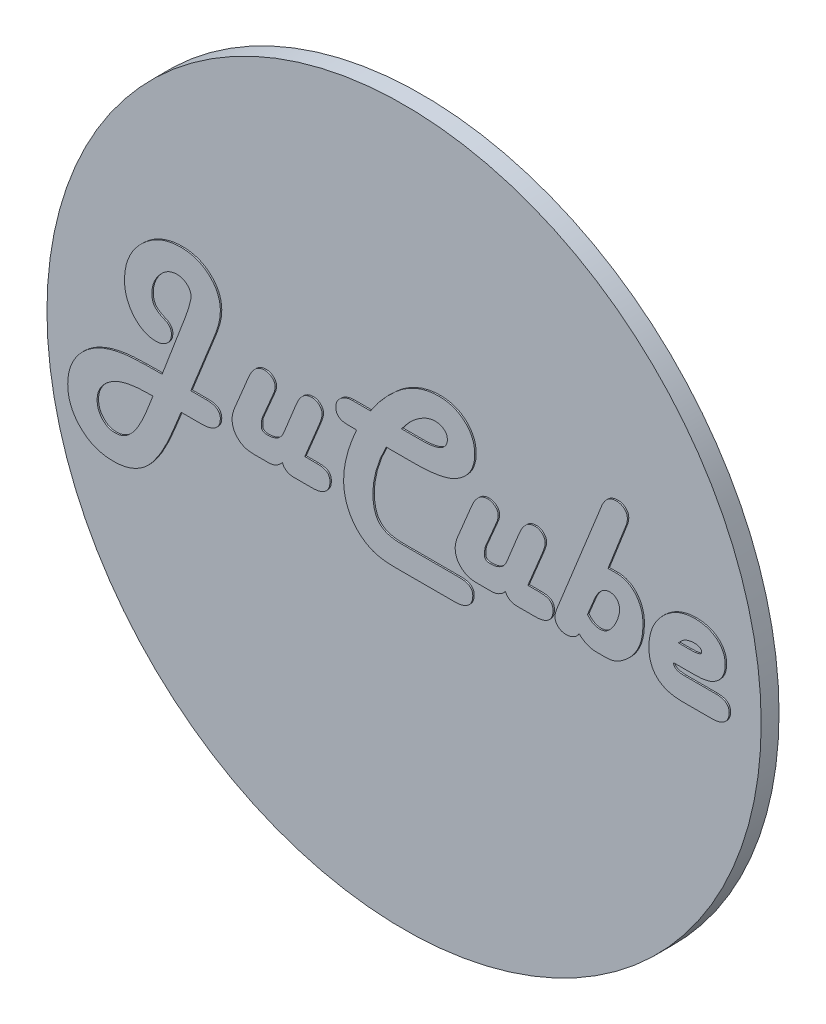
SolidWorks part; units mm, degrees
ref_plane "Front Plane" through (0, 0, 0) normal (0, 0, 1) x (1, 0, 0)
ref_plane "Top Plane" through (0, 0, 0) normal (0, 1, 0) x (1, 0, 0)
ref_plane "Right Plane" through (0, 0, 0) normal (1, 0, 0) x (0, 0, -1)
sketch "Sketch2" plane through (0, 0, 0) normal (0, 0, 1) x (1, 0, 0)
  circle A0 centre (0, 0) radius 63.5
  dimension "D1" = 127
extrude "Boss-Extrude1" add sketch "Sketch2" along normal blind 3.175
sketch "Sketch3" plane through (0, 0, 3.175) normal (0, 0, 1) x (1, 0, 0)
  text T0 "JuCube" font "Harlow Solid Italic" height 25.4
  point P1 (-29.7532, -7.3557)
  point P2 (-48.2437, -18.1195)
  point P3 (-51.4788, -1.2953)
  point P4 (-55.5407, -1.9881)
  point P5 (-59.9004, -3.4138)
extrude "Boss-Extrude2" add sketch "Sketch3" along normal blind 0.254
